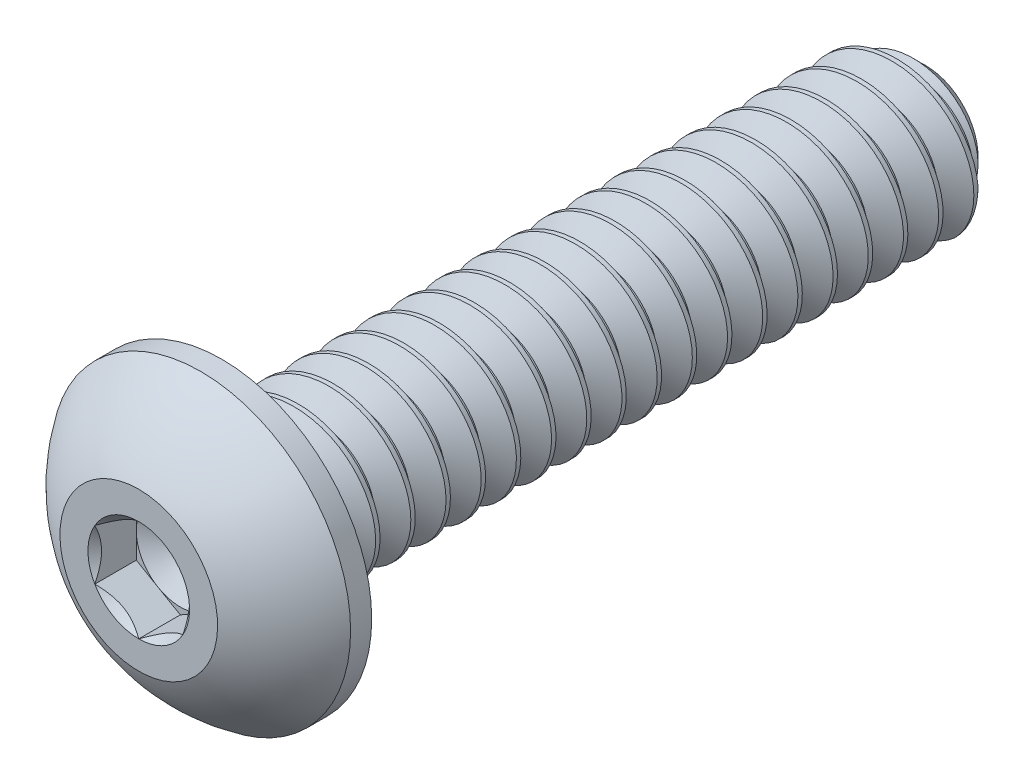
SolidWorks part; units mm, degrees
ref_plane "Front" through (0, 0, 0) normal (0, 0, 1) x (1, 0, 0)
ref_plane "Top" through (0, 0, 0) normal (0, 1, 0) x (1, 0, 0)
ref_plane "Right" through (0, 0, 0) normal (1, 0, 0) x (0, 0, -1)
sketch "Sketch1" plane through (0, 0, 0) normal (1, 0, 0) x (0, 0, -1)
  line L0 (0, 0) -> (-1.4986, 0) construction
  line L1 (0, 0) -> (12.7, 0)
  line L2 (0, 0) -> (0, 1.4224)
  line L3 (0, 1.4224) -> (12.7, 1.4224)
  line L4 (12.7, 0) -> (12.7, 1.4224)
  line L5 (0, -1.4224) -> (12.7, -1.4224) construction
  dimension "D1" = 12.7
  dimension "Thread Dia" = 2.8448
  dimension "Length" = 12.7
  dimension "Head Height" = 1.4986
revolve "Revolve1" add sketch "Sketch1" angle 360 about L0
ref_plane "Plane1" through (0, 0, 1.4986) normal (0, 0, 1) x (1, 0, 0)
chamfer "Chamfer1" distance 0.4763 angle 45 1 edges at (0, 1.4224, -12.7)
sketch "Sketch10" plane through (0, 0, 0) normal (1, 0, 0) x (0, 0, -1)
  line L0 (12.7, 1.4224) -> (13.2556, 1.4224)
  line L1 (13.2556, 1.4224) -> (13.0175, 1.01)
  line L2 (13.0175, 1.01) -> (12.9381, 1.01)
  line L3 (12.9381, 1.01) -> (12.7, 1.4224)
  line L4 (12.8191, 1.2162) -> (13.1366, 1.2162) construction
  dimension "D1" = 60
  dimension "D2" = 0.0794
  dimension "D3" = 0.3175
sketch "Sketch11" plane through (0, 0, -12.7) normal (0, 0, -1) x (-1, 0, 0)
  circle A1 centre (0, 0) radius 0.9462
  circle A2 centre (0, 0) radius 0.9462
  dimension "D1" = 0
curve "Helix/Spiral1" pitch 0.635 height 15.875 turns 25
sweep "Cut-Sweep1" cut profiles "Sketch10" path "Helix/Spiral1"
sketch "Sketch4" plane through (0, 0, 0) normal (0, 0, 1) x (1, 0, 0)
  circle A0 centre (0, 0) radius 2.7051
  dimension "Head Dia" = 5.4102
extrude "Extrude1" add sketch "Sketch4" along normal up to surface (1.4986 mm away) up to plane "Plane1"
sketch "Sketch9" plane through (0, 0, 0) normal (1, 0, 0) x (0, 0, -1)
  line L0 (0, 2.7051) -> (-0.381, 2.7051)
  line L1 (0, 2.7051) -> (0, 3.0861)
  line L2 (0, 3.0861) -> (-1.8796, 3.0861)
  line L3 (0, 0) -> (-1.4986, 0) construction
  line L4 (-1.8796, 3.0861) -> (-1.8796, 1.4224)
  line L5 (-1.8796, 1.4224) -> (-1.4986, 1.4224)
  line L6 (0, 0) -> (0, 1.4224) construction
  line L10 (0, 2.7051) -> (-1.4986, 2.7051) construction
  line L11 (0, 1.4224) -> (12.7, 1.4224) construction
  line L12 (-1.4986, 2.7051) -> (-1.4986, -2.7051) construction
  arc A0 (-1.4986, 1.4224) -> (-0.381, 2.7051) centre (1.4288, 0) cw
  dimension "Side Head Height" = 0.381
revolve "Cut-Revolve3" cut sketch "Sketch9" angle 360 about L3
sketch "Sketch6" plane through (0, 0, 1.4986) normal (0, 0, 1) x (1, 0, 0)
  line L1 (0, -0.9165) -> (0.7937, -0.4583)
  line L2 (0.7937, -0.4583) -> (0.7937, 0.4583)
  line L3 (0.7937, 0.4583) -> (0, 0.9165)
  line L4 (0, 0.9165) -> (-0.7938, 0.4583)
  line L5 (-0.7938, 0.4583) -> (-0.7938, -0.4583)
  line L6 (-0.7938, -0.4583) -> (0, -0.9165)
  circle A0 centre (0, 0) radius 0.7938 construction
  dimension "Hex" = 1.5875
extrude "Cut-Extrude1" cut sketch "Sketch6" against normal blind 0.7493
sketch "Sketch7" plane through (0, 0, 1.4986) normal (0, 0, 1) x (1, 0, 0)
  circle A0 centre (0, 0) radius 0.9165
extrude "Cut-Extrude4" cut sketch "Sketch7" against normal blind 0.7493 draft 45
sketch "Sketch8" plane through (0, 0, 0.7493) normal (0, 0, 1) x (1, 0, 0)
  circle A0 centre (0, 0) radius 0.7938 construction
  circle A1 centre (0, 0) radius 0.7938
extrude "Cut-Extrude5" cut sketch "Sketch8" against normal blind 0.2498 draft 60
sketch "Sketch12" plane through (0, 0, 0) normal (1, 0, 0) x (0, 0, -1)
  line L1 (0, -1.4224) -> (12.7, -1.4224) construction
  spline S2 degree 2 poles (12.2238, 0.013) (12.1819, 0.5945) (12.1444, 1.0058) (12.0915, 1.5865) (12.0385, 1.3739) (11.9856, 1.1614) (11.9327, 0.3681) (11.8798, -0.4251) (11.8269, -1.0058) (11.774, -1.5865) (11.721, -1.3739) (11.6681, -1.1614) (11.6152, -0.3681) (11.5623, 0.4251) (11.5094, 1.0058) (11.4565, 1.5865) (11.4035, 1.3739) (11.3506, 1.1614) (11.2977, 0.3681) (11.2448, -0.4251) (11.1919, -1.0058) (11.139, -1.5865) (11.086, -1.3739) (11.0331, -1.1614) (10.9802, -0.3681) (10.9273, 0.4251) (10.8744, 1.0058) (10.8215, 1.5865) (10.7685, 1.3739) (10.7156, 1.1614) (10.6627, 0.3681) (10.6098, -0.4251) (10.5569, -1.0058) (10.504, -1.5865) (10.451, -1.3739) (10.3981, -1.1614) (10.3452, -0.3681) (10.2923, 0.4251) (10.2394, 1.0058) (10.1865, 1.5865) (10.1335, 1.3739) (10.0806, 1.1614) (10.0277, 0.3681) (9.9748, -0.4251) (9.9219, -1.0058) (9.869, -1.5865) (9.816, -1.3739) (9.7631, -1.1614) (9.7102, -0.3681) (9.6573, 0.4251) (9.6044, 1.0058) (9.5515, 1.5865) (9.4985, 1.3739) (9.4456, 1.1614) (9.3927, 0.3681) (9.3398, -0.4251) (9.2869, -1.0058) (9.234, -1.5865) (9.181, -1.3739) (9.1281, -1.1614) (9.0752, -0.3681) (9.0223, 0.4251) (8.9694, 1.0058) (8.9165, 1.5865) (8.8635, 1.3739) (8.8106, 1.1614) (8.7577, 0.3681) (8.7048, -0.4251) (8.6519, -1.0058) (8.599, -1.5865) (8.546, -1.3739) (8.4931, -1.1614) (8.4402, -0.3681) (8.3873, 0.4251) (8.3344, 1.0058) (8.2815, 1.5865) (8.2285, 1.3739) (8.1756, 1.1614) (8.1227, 0.3681) (8.0698, -0.4251) (8.0169, -1.0058) (7.964, -1.5865) (7.911, -1.3739) (7.8581, -1.1614) (7.8052, -0.3681) (7.7523, 0.4251) (7.6994, 1.0058) (7.6465, 1.5865) (7.5935, 1.3739) (7.5406, 1.1614) (7.4877, 0.3681) (7.4348, -0.4251) (7.3819, -1.0058) (7.329, -1.5865) (7.276, -1.3739) (7.2231, -1.1614) (7.1702, -0.3681) (7.1173, 0.4251) (7.0644, 1.0058) (7.0115, 1.5865) (6.9585, 1.3739) (6.9056, 1.1614) (6.8527, 0.3681) (6.7998, -0.4251) (6.7469, -1.0058) (6.694, -1.5865) (6.641, -1.3739) (6.5881, -1.1614) (6.5352, -0.3681) (6.4823, 0.4251) (6.4294, 1.0058) (6.3765, 1.5865) (6.3235, 1.3739) (6.2706, 1.1614) (6.2177, 0.3681) (6.1648, -0.4251) (6.1119, -1.0058) (6.059, -1.5865) (6.006, -1.3739) (5.9531, -1.1614) (5.9002, -0.3681) (5.8473, 0.4251) (5.7944, 1.0058) (5.7415, 1.5865) (5.6885, 1.3739) (5.6356, 1.1614) (5.5827, 0.3681) (5.5298, -0.4251) (5.4769, -1.0058) (5.424, -1.5865) (5.371, -1.3739) (5.3181, -1.1614) (5.2652, -0.3681) (5.2123, 0.4251) (5.1594, 1.0058) (5.1065, 1.5865) (5.0535, 1.3739) (5.0006, 1.1614) (4.9477, 0.3681) (4.8948, -0.4251) (4.8419, -1.0058) (4.789, -1.5865) (4.736, -1.3739) (4.6831, -1.1614) (4.6302, -0.3681) (4.5773, 0.4251) (4.5244, 1.0058) (4.4715, 1.5865) (4.4185, 1.3739) (4.3656, 1.1614) (4.3127, 0.3681) (4.2598, -0.4251) (4.2069, -1.0058) (4.154, -1.5865) (4.101, -1.3739) (4.0481, -1.1614) (3.9952, -0.3681) (3.9423, 0.4251) (3.8894, 1.0058) (3.8365, 1.5865) (3.7835, 1.3739) (3.7306, 1.1614) (3.6777, 0.3681) (3.6248, -0.4251) (3.5719, -1.0058) (3.519, -1.5865) (3.466, -1.3739) (3.4131, -1.1614) (3.3602, -0.3681) (3.3073, 0.4251) (3.2544, 1.0058) (3.2015, 1.5865) (3.1485, 1.3739) (3.0956, 1.1614) (3.0427, 0.3681) (2.9898, -0.4251) (2.9369, -1.0058) (2.884, -1.5865) (2.831, -1.3739) (2.7781, -1.1614) (2.7252, -0.3681) (2.6723, 0.4251) (2.6194, 1.0058) (2.5665, 1.5865) (2.5135, 1.3739) (2.4606, 1.1614) (2.4077, 0.3681) (2.3548, -0.4251) (2.3019, -1.0058) (2.249, -1.5865) (2.196, -1.3739) (2.1431, -1.1614) (2.0902, -0.3681) (2.0373, 0.4251) (1.9844, 1.0058) (1.9315, 1.5865) (1.8785, 1.3739) (1.8256, 1.1614) (1.7727, 0.3681) (1.7198, -0.4251) (1.6669, -1.0058) (1.614, -1.5865) (1.561, -1.3739) (1.5081, -1.1614) (1.4552, -0.3681) (1.4023, 0.4251) (1.3494, 1.0058) (1.2965, 1.5865) (1.2435, 1.3739) (1.1906, 1.1614) (1.1377, 0.3681) (1.0848, -0.4251) (1.0319, -1.0058) (0.979, -1.5865) (0.926, -1.3739) (0.8731, -1.1614) (0.8202, -0.3681) (0.7673, 0.4251) (0.7144, 1.0058) (0.6615, 1.5865) (0.6085, 1.3739) (0.5556, 1.1614) (0.5027, 0.3681) (0.4498, -0.4251) (0.3969, -1.0058) (0.344, -1.5865) (0.291, -1.3739) (0.2381, -1.1614) (0.1852, -0.3681) (0.1323, 0.4251) (0.0794, 1.0058) (0.0419, 1.417) (0, 1.4223) knots 0.035087 0.035087 0.035087 0.04 0.04 0.046667 0.046667 0.053333 0.053333 0.06 0.06 0.066667 0.066667 0.073333 0.073333 0.08 0.08 0.086667 0.086667 0.093333 0.093333 0.1 0.1 0.106667 0.106667 0.113333 0.113333 0.12 0.12 0.126667 0.126667 0.133333 0.133333 0.14 0.14 0.146667 0.146667 0.153333 0.153333 0.16 0.16 0.166667 0.166667 0.173333 0.173333 0.18 0.18 0.186667 0.186667 0.193333 0.193333 0.2 0.2 0.206667 0.206667 0.213333 0.213333 0.22 0.22 0.226667 0.226667 0.233333 0.233333 0.24 0.24 0.246667 0.246667 0.253333 0.253333 0.26 0.26 0.266667 0.266667 0.273333 0.273333 0.28 0.28 0.286667 0.286667 0.293333 0.293333 0.3 0.3 0.306667 0.306667 0.313333 0.313333 0.32 0.32 0.326667 0.326667 0.333333 0.333333 0.34 0.34 0.346667 0.346667 0.353333 0.353333 0.36 0.36 0.366667 0.366667 0.373333 0.373333 0.38 0.38 0.386667 0.386667 0.393333 0.393333 0.4 0.4 0.406667 0.406667 0.413333 0.413333 0.42 0.42 0.426667 0.426667 0.433333 0.433333 0.44 0.44 0.446667 0.446667 0.453333 0.453333 0.46 0.46 0.466667 0.466667 0.473333 0.473333 0.48 0.48 0.486667 0.486667 0.493333 0.493333 0.5 0.5 0.506667 0.506667 0.513333 0.513333 0.52 0.52 0.526667 0.526667 0.533333 0.533333 0.54 0.54 0.546667 0.546667 0.553333 0.553333 0.56 0.56 0.566667 0.566667 0.573333 0.573333 0.58 0.58 0.586667 0.586667 0.593333 0.593333 0.6 0.6 0.606667 0.606667 0.613333 0.613333 0.62 0.62 0.626667 0.626667 0.633333 0.633333 0.64 0.64 0.646667 0.646667 0.653333 0.653333 0.66 0.66 0.666667 0.666667 0.673333 0.673333 0.68 0.68 0.686667 0.686667 0.693333 0.693333 0.7 0.7 0.706667 0.706667 0.713333 0.713333 0.72 0.72 0.726667 0.726667 0.733333 0.733333 0.74 0.74 0.746667 0.746667 0.753333 0.753333 0.76 0.76 0.766667 0.766667 0.773333 0.773333 0.78 0.78 0.786667 0.786667 0.793333 0.793333 0.8 0.8 0.804913 0.804913 0.804913 weights 0.948065 0.901259 1 0.866025 1 0.866025 1 0.866025 1 0.866025 1 0.866025 1 0.866025 1 0.866025 1 0.866025 1 0.866025 1 0.866025 1 0.866025 1 0.866025 1 0.866025 1 0.866025 1 0.866025 1 0.866025 1 0.866025 1 0.866025 1 0.866025 1 0.866025 1 0.866025 1 0.866025 1 0.866025 1 0.866025 1 0.866025 1 0.866025 1 0.866025 1 0.866025 1 0.866025 1 0.866025 1 0.866025 1 0.866025 1 0.866025 1 0.866025 1 0.866025 1 0.866025 1 0.866025 1 0.866025 1 0.866025 1 0.866025 1 0.866025 1 0.866025 1 0.866025 1 0.866025 1 0.866025 1 0.866025 1 0.866025 1 0.866025 1 0.866025 1 0.866025 1 0.866025 1 0.866025 1 0.866025 1 0.866025 1 0.866025 1 0.866025 1 0.866025 1 0.866025 1 0.866025 1 0.866025 1 0.866025 1 0.866025 1 0.866025 1 0.866025 1 0.866025 1 0.866025 1 0.866025 1 0.866025 1 0.866025 1 0.866025 1 0.866025 1 0.866025 1 0.866025 1 0.866025 1 0.866025 1 0.866025 1 0.866025 1 0.866025 1 0.866025 1 0.866025 1 0.866025 1 0.866025 1 0.866025 1 0.866025 1 0.866025 1 0.866025 1 0.866025 1 0.866025 1 0.866025 1 0.866025 1 0.866025 1 0.866025 1 0.866025 1 0.866025 1 0.866025 1 0.866025 1 0.866025 1 0.866025 1 0.866025 1 0.866025 1 0.866025 1 0.866025 1 0.866025 1 0.866025 1 0.866025 1 0.866025 1 0.866025 1 0.866025 1 0.866025 1 0.866025 1 0.866025 1 0.866025 1 0.866025 1 0.866025 1 0.901259 0.948065 construction
  point P0 (11.7466, -1.4224)
equation "\"D1@Cut-Extrude1\"=\"Head Height@Sketch1\"/2"
equation "\"D1@Cut-Extrude4\"=\"D1@Cut-Extrude1\""
equation "\"D1@Cut-Extrude5\"=\"D1@Cut-Extrude1\"/3"
equation "\"D3@Helix/Spiral1\" = \"Length@Sketch1\" + .125"
equation "\"D1@Chamfer1\" = \"D4@Helix/Spiral1\" * .75"
equation "\"D2@Sketch10\" = \"D4@Helix/Spiral1\" * .125"
equation "\"D3@Sketch10\" = \"D4@Helix/Spiral1\" * .5"
